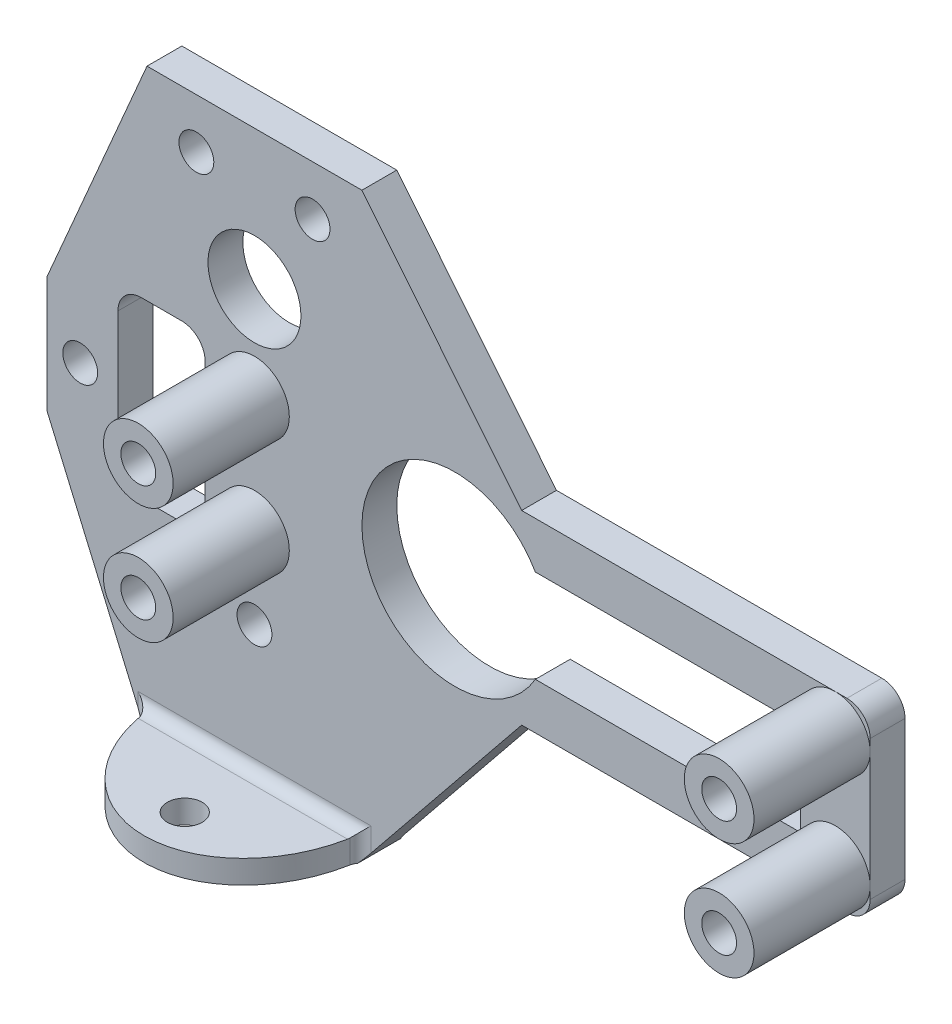
SolidWorks part; units mm, degrees
material "1060 Alloy"
ref_plane "Front Plane" through (0, 0, 0) normal (0, 0, 1) x (1, 0, 0)
ref_plane "Top Plane" through (0, 0, 0) normal (0, 1, 0) x (1, 0, 0)
ref_plane "Right Plane" through (0, 0, 0) normal (1, 0, 0) x (0, 0, -1)
sketch "Sketch1" plane through (0, 0, 0) normal (0, 0, 1) x (1, 0, 0)
  line L0 (9.25, 30) -> (23, 13) construction
  line L1 (0, 0) -> (50, 0) construction
  line L2 (0, 0) -> (0, 10) construction
  line L3 (0, 10) -> (50, 10) construction
  line L4 (50, 0) -> (50, 10) construction
  line L5 (9.25, -20) -> (-9.25, -20) construction
  line L6 (9.25, -20) -> (9.25, 30) construction
  line L7 (9.25, 30) -> (-9.25, 30) construction
  line L8 (-9.25, -20) -> (-9.25, 30) construction
  line L9 (9.25, -20) -> (-9.25, 30) construction
  line L10 (9.25, 30) -> (-9.25, -20) construction
  line L11 (-53, -3) -> (53, -3) construction
  line L12 (-53, -3) -> (-53, 13) construction
  line L13 (-53, 13) -> (53, 13) construction
  line L14 (53, -3) -> (53, 13) construction
  line L15 (-53, -3) -> (53, 13) construction
  line L16 (-53, 13) -> (53, -3) construction
  line L17 (9.25, -20) -> (23, -3) construction
  line L18 (9.25, 30) -> (23, 13)
  line L19 (-47, 1) -> (47, 1) construction
  line L20 (-47, 1) -> (-47, 9) construction
  line L21 (-47, 9) -> (47, 9) construction
  line L22 (47, 1) -> (47, 9) construction
  line L23 (-47, 1) -> (47, 9) construction
  line L24 (-47, 9) -> (47, 1) construction
  line L25 (23, 13) -> (53, 13)
  line L26 (53, 13) -> (53, -3)
  line L27 (53, -3) -> (23, -3)
  line L28 (23, -3) -> (9.25, -20)
  line L29 (7, 10) -> (7, 1) construction
  line L30 (0, 5) -> (53, 5) construction
  line L31 (47, 9) -> (24.1782, 9)
  line L32 (47, 9) -> (47, 1)
  line L33 (47, 1) -> (24.1782, 1)
  line L34 (9.25, 30) -> (-9.25, 30)
  line L35 (9.25, -20) -> (-9.25, -20)
  line L36 (0, 5) -> (-8, 5) construction
  line L37 (0, 30) -> (0, -20) construction
  line L38 (-4.25, -2.5) -> (-11.75, -2.5)
  line L39 (-4.25, -2.5) -> (-4.25, 12.5)
  line L40 (-4.25, 12.5) -> (-11.75, 12.5)
  line L41 (-11.75, -2.5) -> (-11.75, 12.5)
  line L42 (-4.25, -2.5) -> (-11.75, 12.5) construction
  line L43 (-4.25, 12.5) -> (-11.75, -2.5) construction
  line L44 (-15, 13) -> (-15, -3) construction
  line L45 (-8, 5) -> (-40.5914, 5) construction
  line L46 (-17.86, -3) -> (-17.86, 14.3339) construction
  line L47 (-17.86, 5.667) -> (-17.86, 10)
  line L48 (-9.25, 30) -> (-17.86, 10)
  line L49 (-9.25, -20) -> (-17.86, 0)
  line L50 (-17.86, 10) -> (-17.86, 0)
  circle A0 centre (17.25, 5) radius 8 construction
  circle A1 centre (50, 10) radius 1.5
  circle A2 centre (50, 0) radius 1.5
  arc A3 (24.1782, 9) -> (24.1782, 1) centre (17.25, 5) ccw
  circle A4 centre (0, 10) radius 1.5
  circle A5 centre (0, 0) radius 1.5
  circle A6 centre (0, 18) radius 4
  circle A7 centre (0, -7) radius 1.5
  circle A8 centre (-15, 5) radius 1.5
  point P5 (0, 5)
  point P10 (0, 5)
  point P15 (0, 5)
  dimension "D13" = 16
  dimension "D14" = 3
  dimension "D15" = 3
  dimension "D16" = 3
  dimension "D17" = 3
  dimension "D21" = 8
  dimension "D23" = 3
  dimension "D24" = 13
  dimension "D26" = 3
  dimension "D1" = 10
  dimension "D2" = 50
  dimension "D3" = 50
  dimension "D4" = 18.5
  dimension "D5" = 16
  dimension "D6" = 3
  dimension "D7" = 30
  dimension "D8" = 30
  dimension "D9" = 8
  dimension "D10" = 6
  dimension "D11" = 40
  dimension "D12" = 0
  dimension "D18" = 8
  dimension "D19" = 15
  dimension "D20" = 7.5
  dimension "D22" = 12
  dimension "D25" = 15
  dimension "D27" = 70.86
  dimension "D28" = 10
  dimension "D29" = 5
extrude "Boss-Extrude1" add sketch "Sketch1" along normal blind 3 contours L47 L50 L49 L35 L28 L27 L26 L25 L18 L34 L48 A8 A7 A6 A5 A4 A3 L31 L32 L33 A2 A1 L38 L41 L40 L39 region at (7.9808, 4.6293, 0)
fillet "Fillet1" radius 2 6 edges at (53, 13, 1.5) (53, -3, 1.5) (-4.25, -2.5, 1.5) (-11.75, -2.5, 1.5) (-4.25, 12.5, 1.5) (-11.75, 12.5, 1.5)
sketch "Sketch2" plane through (0, 0, 3) normal (0, 0, 1) x (1, 0, 0)
  line L0 (0, 30) -> (0, -20) construction
  line L1 (9.25, 30) -> (-9.25, 30) construction
  line L2 (9.25, -20) -> (-9.25, -20) construction
  line L4 (0, 10) -> (50, 10) construction
  line L5 (0, 10) -> (0, 0) construction
  line L6 (0, 0) -> (50, 0) construction
  line L7 (50, 10) -> (50, 0) construction
  circle A0 centre (0, 10) radius 3
  circle A1 centre (0, 10) radius 1.5
  circle A2 centre (50, 10) radius 1.5
  circle A3 centre (50, 10) radius 3
  circle A4 centre (50, 0) radius 1.5
  circle A5 centre (50, 0) radius 3
  circle A6 centre (0, 0) radius 1.5
  circle A7 centre (0, 0) radius 3
  dimension "D1" = 6
  dimension "D2" = 2
  dimension "D3" = 2
extrude "Boss-Extrude2" add sketch "Sketch2" along normal blind 10
sketch "Sketch3" plane through (0, -20, 0) normal (0, -1, 0) x (1, 0, 0)
  line L0 (-9.25, 3) -> (9.25, 0) construction
  line L1 (9.25, 0) -> (9.25, 3) construction
  line L2 (9.25, 3) -> (-9.25, 0) construction
  line L3 (-9.25, 3) -> (-9.25, 0) construction
  ellipse E0 centre (0, 1.5) end of major axis (0, -9.5) minor radius 9.25
extrude "Boss-Extrude3" add sketch "Sketch3" against normal blind 2
fillet "Fillet2" radius 1 4 edges at (9.1636, -19, 3) (-9.1636, -19, 3) (-9.1636, -19, 0) (9.1636, -19, 0)
fillet "Fillet3" radius 1 2 edges at (0, -18, 0) (0, -18, 3)
sketch "Sketch4" plane through (0, -20, 0) normal (0, -1, 0) x (-1, 0, 0)
  line L0 (-10.0256, -3) -> (10.0256, -3) construction
  line L1 (10.0256, -3) -> (10.0256, 0) construction
  line L2 (10.0256, 0) -> (-10.0256, 0) construction
  line L3 (-10.0256, 0) -> (-10.0256, -3) construction
  line L4 (-10.0256, -3) -> (10.0256, 0) construction
  line L5 (10.0256, 0) -> (-10.0256, 0) construction
  line L6 (-10.0256, 0) -> (10.0256, -3) construction
  circle A0 centre (0, -1.5) radius 7.5 construction
  circle A1 centre (0, -9) radius 1.5
  circle A2 centre (0, 6) radius 1.5
  dimension "D1" = 15
  dimension "D2" = 3
  dimension "D3" = 3
extrude "Cut-Extrude1" cut sketch "Sketch4" against normal up to next
sketch "Sketch5" plane through (0, 0, 3) normal (0, 0, 1) x (1, 0, 0)
  line L0 (0, 30) -> (0, -20) construction
  line L1 (9.25, 30) -> (-9.25, 30) construction
  line L2 (-9.0417, -20) -> (9.0417, -20) construction
  line L3 (-11.0958, 25.7123) -> (12.718, 25.7123) construction
  line L4 (-9.25, 30) -> (-17.86, 10) construction
  line L5 (9.25, 30) -> (23, 13) construction
  line L6 (-5, 25.7123) -> (-15, 5)
  circle A0 centre (-5, 25.7123) radius 1.5
  circle A1 centre (5, 25.7123) radius 1.5
  dimension "D3" = 3
  dimension "D1" = 23
  dimension "D2" = 5
extrude "Cut-Extrude2" cut sketch "Sketch5" against normal up to next contours A0 | A1 region at (-4.2251, 24.4778, 3) region at (5, 25.7123, 3)
